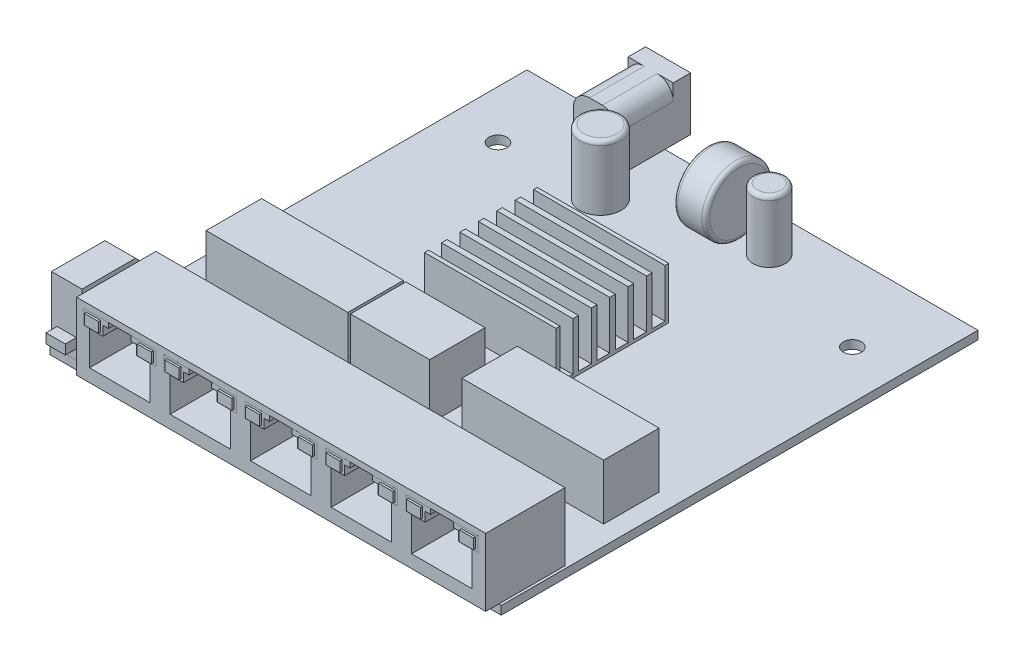
SolidWorks part; units mm, degrees
ref_plane "Front Plane" through (0, 0, 0) normal (0, 0, 1) x (1, 0, 0)
ref_plane "Top Plane" through (0, 0, 0) normal (0, 1, 0) x (1, 0, 0)
ref_plane "Right Plane" through (0, 0, 0) normal (1, 0, 0) x (0, 0, -1)
sketch "Sketch1" plane through (0, 0, 0) normal (0, 1, 0) x (1, 0, 0)
  line L1 (0, 0) -> (88.9, 0)
  line L2 (0, 0) -> (0, -93.98)
  line L3 (0, -93.98) -> (88.9, -93.98)
  line L4 (88.9, 0) -> (88.9, -93.98)
  dimension "D1" = 88.9
  dimension "D2" = 93.98
extrude "Extrude1" add sketch "Sketch1" along normal blind 1.651
sketch "Sketch2" plane through (0, 1.651, 0) normal (0, 1, 0) x (1, 0, 0)
  line L0 (0, -93.98) -> (88.9, -93.98) construction
  line L1 (0.254, -93.98) -> (6.2738, -93.98)
  line L2 (0.254, -93.98) -> (0.254, -80.264)
  line L3 (0.254, -80.264) -> (6.2738, -80.264)
  line L4 (6.2738, -93.98) -> (6.2738, -80.264)
  line L5 (0, 0) -> (0, -93.98) construction
  dimension "D1" = 6.0198
  dimension "D2" = 13.716
  dimension "D3" = 0.254
extrude "Extrude2" add sketch "Sketch2" along normal blind 12.7 separate body
chamfer "Chamfer1" distance 3.175 angle 45 1 edges at (3.2639, 14.351, 80.264)
sketch "Sketch3" plane through (0, 0, 93.98) normal (0, 0, 1) x (1, 0, 0)
  line L0 (0.254, 1.651) -> (6.2738, 1.651) construction
  line L1 (1.3589, 5.5245) -> (5.1689, 5.5245)
  line L2 (1.3589, 5.5245) -> (1.3589, 3.6195)
  line L3 (1.3589, 3.6195) -> (5.1689, 3.6195)
  line L4 (5.1689, 5.5245) -> (5.1689, 3.6195)
  line L5 (3.2639, 1.651) -> (3.2639, 3.6195) construction
  dimension "D1" = 3.81
  dimension "D2" = 1.905
  dimension "D3" = 1.9685
extrude "Extrude3" add sketch "Sketch3" along normal blind 2.1844
sketch "Sketch4" plane through (0, 1.651, 0) normal (0, 1, 0) x (1, 0, 0)
  line L1 (7.747, -80.899) -> (88.392, -80.899)
  line L2 (7.747, -80.899) -> (7.747, -96.52)
  line L3 (7.747, -96.52) -> (88.392, -96.52)
  line L4 (88.392, -80.899) -> (88.392, -96.52)
  line L5 (0, -93.98) -> (88.9, -93.98) construction
  line L7 (0, 0) -> (0, -93.98) construction
  dimension "D1" = 80.645
  dimension "D2" = 7.747
  dimension "D3" = 15.621
  dimension "D4" = 2.54
extrude "Extrude4" add sketch "Sketch4" along normal blind 13.335 separate body
sketch "Sketch6" plane through (0, 0, 96.52) normal (0, 0, 1) x (1, 0, 0)
  line L0 (7.747, 1.651) -> (88.392, 1.651) construction
  line L1 (7.747, 14.986) -> (7.747, 1.651) construction
  line L2 (16.256, 4.191) -> (16.256, 13.7922) construction
  line L4 (14.0208, 12.7762) -> (14.0208, 13.7922)
  line L5 (14.0208, 13.7922) -> (18.4912, 13.7922)
  line L6 (18.4912, 12.7762) -> (18.4912, 13.7922)
  line L7 (14.0208, 12.7762) -> (12.954, 12.7762)
  line L28 (10.287, 10.922) -> (10.287, 4.191)
  line L29 (10.287, 4.191) -> (22.225, 4.191)
  line L30 (22.225, 4.191) -> (22.225, 10.922)
  line L33 (19.558, 12.7762) -> (18.4912, 12.7762)
  line L60 (10.287, 10.922) -> (12.954, 10.922)
  line L61 (12.954, 10.922) -> (12.954, 12.7762)
  line L70 (19.558, 12.7762) -> (19.558, 10.922)
  line L71 (19.558, 10.922) -> (22.225, 10.922)
  dimension "D1" = 2.54
  dimension "D2" = 8.5852
  dimension "D3" = 6.731
  dimension "D4" = 11.938
  dimension "D5" = 6.604
  dimension "D6" = 2.54
  dimension "D7" = 4.4704
  dimension "D8" = 1.016
extrude "Cut-Extrude1" cut sketch "Sketch6" against normal blind 11.43
sketch "Sketch8" plane through (0, 0, 96.52) normal (0, 0, 1) x (1, 0, 0)
  line L0 (14.0208, 13.7922) -> (18.4912, 13.7922) construction
  line L1 (12.954, 10.922) -> (9.144, 10.922)
  line L2 (12.954, 10.922) -> (12.954, 12.7762)
  line L3 (12.954, 13.7922) -> (9.144, 13.7922)
  line L4 (9.144, 10.922) -> (9.144, 13.7922)
  line L5 (19.558, 10.922) -> (23.368, 10.922)
  line L6 (19.558, 10.922) -> (19.558, 12.7762)
  line L7 (19.558, 13.7922) -> (23.368, 13.7922)
  line L8 (23.368, 10.922) -> (23.368, 13.7922)
  line L9 (11.049, 13.7922) -> (11.049, 13.3731) construction
  line L10 (9.652, 13.3731) -> (12.446, 13.3731)
  line L11 (9.652, 13.3731) -> (9.652, 11.3411)
  line L12 (9.652, 11.3411) -> (12.446, 11.3411)
  line L13 (12.446, 13.3731) -> (12.446, 11.3411)
  line L14 (20.066, 13.3731) -> (22.86, 13.3731)
  line L15 (20.066, 13.3731) -> (20.066, 11.3411)
  line L16 (20.066, 11.3411) -> (22.86, 11.3411)
  line L17 (22.86, 13.3731) -> (22.86, 11.3411)
  line L18 (9.144, 12.3571) -> (9.652, 12.3571) construction
  line L19 (21.463, 13.7922) -> (21.463, 13.3731) construction
  line L21 (14.0208, 12.7762) -> (12.954, 12.7762)
  line L22 (14.0208, 12.7762) -> (14.0208, 13.7922)
  line L23 (14.0208, 13.7922) -> (12.954, 13.7922)
  line L25 (18.4912, 12.7762) -> (19.558, 12.7762)
  line L26 (18.4912, 12.7762) -> (18.4912, 13.7922)
  line L27 (18.4912, 13.7922) -> (19.558, 13.7922)
  dimension "D1" = 3.81
  dimension "D2" = 2.794
  dimension "D3" = 2.032
extrude "Extrude5" add sketch "Sketch8" along normal blind 0.3969 contours L13 L10 L11 L12 | L17 L14 L15 L16 region at (11.049, 12.3571, 96.52) region at (21.463, 12.3571, 96.52)
extrude "Extrude13" add sketch "Sketch8<3>" along normal blind 0.0013
sketch "Sketch8<3>" plane through (0, 0, 96.52) normal (0, 0, 1) x (1, 0, 0) same geometry as "Sketch8"
pattern_linear "LPattern2" count 5 spacing 15.875 along (1, 0, 0) of "Cut-Extrude1", "Extrude5", "Extrude13"
sketch "Sketch9" plane through (0, 1.651, 0) normal (0, 1, 0) x (1, 0, 0)
  line L0 (88.9, -93.98) -> (88.9, 0) construction
  line L1 (6.731, -59.055) -> (34.671, -59.055)
  line L2 (6.731, -59.055) -> (6.731, -69.977)
  line L3 (6.731, -69.977) -> (34.671, -69.977)
  line L4 (34.671, -59.055) -> (34.671, -69.977)
  line L5 (35.179, -59.055) -> (50.8, -59.055)
  line L6 (35.179, -59.055) -> (35.179, -69.977)
  line L7 (35.179, -69.977) -> (50.8, -69.977)
  line L8 (50.8, -59.055) -> (50.8, -69.977)
  line L9 (57.15, -59.055) -> (85.09, -59.055)
  line L10 (57.15, -59.055) -> (57.15, -69.977)
  line L11 (57.15, -69.977) -> (85.09, -69.977)
  line L12 (85.09, -59.055) -> (85.09, -69.977)
  line L13 (88.9, 0) -> (0, 0) construction
  dimension "D1" = 27.94
  dimension "D2" = 15.621
  dimension "D3" = 27.94
  dimension "D4" = 10.922
  dimension "D5" = 3.81
  dimension "D6" = 6.35
  dimension "D7" = 0.508
  dimension "D8" = 59.055
extrude "Extrude6" add sketch "Sketch9" along normal blind 10.922 separate body
sketch "Sketch10" plane through (0, 1.651, 0) normal (0, 1, 0) x (1, 0, 0)
  line L0 (88.9, -93.98) -> (88.9, 0) construction
  line L1 (31.242, -29.21) -> (57.15, -29.21)
  line L2 (31.242, -29.21) -> (31.242, -51.435)
  line L3 (31.242, -51.435) -> (57.15, -51.435)
  line L4 (57.15, -29.21) -> (57.15, -51.435)
  line L5 (88.9, 0) -> (0, 0) construction
  dimension "D1" = 25.908
  dimension "D2" = 22.225
  dimension "D3" = 31.75
  dimension "D4" = 29.21
extrude "Extrude7" add sketch "Sketch10" along normal blind 10.16 separate body
sketch "Sketch11" plane through (57.15, 0, 0) normal (1, 0, 0) x (0, 0, -1)
  line L0 (-51.435, 11.811) -> (-29.21, 11.811) construction
  line L1 (-50.6412, 11.811) -> (-48.1012, 11.811)
  line L2 (-50.6412, 11.811) -> (-50.6412, 2.286)
  line L3 (-50.6412, 2.286) -> (-48.1012, 2.286)
  line L4 (-48.1012, 11.811) -> (-48.1012, 2.286)
  line L5 (-51.435, 11.811) -> (-51.435, 1.651) construction
  dimension "D1" = 2.54
  dimension "D2" = 0.7937
  dimension "D3" = 9.525
extrude "Extrude8" cut sketch "Sketch11" against normal up to next (25.908 mm away)
pattern_linear "LPattern1" count 6 spacing 3.6322 along (0, 0, -1) of "Extrude8"
sketch "Sketch12" plane through (0, 1.651, 0) normal (0, 1, 0) x (1, 0, 0)
  line L0 (88.9, 0) -> (0, 0) construction
  line L1 (18.288, 5.08) -> (27.178, 5.08)
  line L2 (18.288, 5.08) -> (18.288, -9.144)
  line L3 (18.288, -9.144) -> (27.178, -9.144)
  line L4 (27.178, 5.08) -> (27.178, -9.144)
  line L5 (0, 0) -> (0, -93.98) construction
  dimension "D1" = 14.224
  dimension "D2" = 8.89
  dimension "D3" = 5.08
  dimension "D4" = 18.288
extrude "Extrude9" add sketch "Sketch12" along normal blind 10.541 separate body
sketch "Sketch14" plane through (0, 0, 9.144) normal (0, 0, 1) x (1, 0, 0)
  line L0 (18.288, 12.192) -> (27.178, 12.192) construction
  line L1 (21.463, 12.192) -> (18.288, 12.192)
  line L4 (18.288, 1.651) -> (27.178, 1.651)
  line L5 (27.178, 1.651) -> (27.178, 12.192)
  line L6 (27.178, 12.192) -> (18.288, 12.192)
  line L7 (18.288, 12.192) -> (18.288, 1.651)
  line L9 (27.178, 9.017) -> (27.178, 12.192)
  line L10 (27.178, 12.192) -> (24.003, 12.192)
  line L11 (18.288, 12.192) -> (18.288, 9.017)
  arc A0 (18.288, 9.017) -> (21.463, 12.192) centre (21.463, 9.017) cw
  arc A1 (24.003, 12.192) -> (27.178, 9.017) centre (24.003, 9.017) cw
  dimension "D2" = 3.175
  dimension "D1" = 0
extrude "Extrude10" cut sketch "Sketch14" against normal offset from surface (10.795 mm away) 3.429 up to face at (22.733, 6.9215, -5.08)
sketch "Sketch15" plane through (0, 0, -5.08) normal (0, 0, -1) x (-1, 0, 0)
  line L0 (-22.733, 1.651) -> (-22.733, 4.826) construction
  line L1 (-27.178, 1.651) -> (-18.288, 1.651) construction
  circle A0 centre (-22.733, 8.001) radius 3.175
  dimension "D2" = 6.35
  dimension "D1" = 3.175
extrude "Extrude11" cut sketch "Sketch15" against normal blind 8.89
sketch "Sketch16" plane through (0, 0, 3.81) normal (0, 0, -1) x (-1, 0, 0)
  circle A0 centre (-22.733, 8.001) radius 0.7937
  dimension "D1" = 1.5875
extrude "Extrude12" add sketch "Sketch16" along normal offset from surface (7.62 mm away) 1.27 up to face at (19.558, 8.001, -5.08)
fillet "Fillet1" radius 0.7937 1 edges at (23.5267, 8.001, -3.81)
hole_wizard "9/64 (0.14063) Diameter Hole1" positions "Sketch18" profile "Sketch17" hole size "9/64" standard "Ansi Inch" end condition through all
sketch "Sketch18" plane through (0, 1.651, 0) normal (0, 1, 0) x (-1, 0, 0)
  line L0 (-88.9, 0) -> (0, 0) construction
  line L1 (-44.45, 0) -> (-44.45, 16.0377) construction
  point P0 (-9.525, 15.24)
  point P2 (-79.375, 15.24)
  dimension "D1" = 69.85
  dimension "D2" = 15.24
sketch "Sketch17" plane through (9.525, 1.651, 15.24) normal (1, 0, 0) x (0, 0, 1)
  line L0 (0, 0) -> (0, 1.651)
  line L1 (0, 1.651) -> (1.786, 1.651)
  line L2 (1.786, 1.651) -> (1.786, 0)
  line L5 (1.786, 0) -> (0, 0)
  line L11 (0, -6.35) -> (0, 107.95) construction
  dimension "Thru Hole Dia." = 3.572
  dimension "Thru Hole Depth" = 1.651
sketch "Sketch19" plane through (0, 1.651, 0) normal (0, 1, 0) x (1, 0, 0)
  line L0 (0, 0) -> (0, -93.98) construction
  line L1 (88.9, 0) -> (0, 0) construction
  circle A0 centre (29.21, -14.732) radius 4.064
  dimension "D1" = 8.128
  dimension "D2" = 29.21
  dimension "D3" = 14.732
extrude "Extrude14" add sketch "Sketch19" along normal blind 12.7 separate body
fillet "Fillet2" radius 0.7937 1 edges at (29.21, 14.351, 18.796)
sketch "Sketch20" plane through (0, 1.651, 0) normal (0, 1, 0) x (1, 0, 0)
  line L0 (0, 0) -> (0, -93.98) construction
  line L1 (88.9, 0) -> (0, 0) construction
  circle A0 centre (55.372, -7.62) radius 3.175
  dimension "D1" = 6.35
  dimension "D2" = 55.372
  dimension "D3" = 7.62
extrude "Extrude15" add sketch "Sketch20" along normal blind 12.192 separate body
fillet "Fillet3" radius 0.7937 1 edges at (55.372, 13.843, 10.795)
ref_plane "Plane1" through (46.99, 0, 0) normal (-1, 0, 0) x (0, 0, 1)
sketch "Sketch21" plane through (46.99, 0, 0) normal (-1, 0, 0) x (0, 0, 1)
  line L0 (0, 1.651) -> (93.98, 1.651) construction
  line L2 (0, 1.651) -> (0, 0) construction
  circle A0 centre (8.255, 8.3185) radius 6.6675
  dimension "D1" = 13.335
  dimension "D2" = 8.255
extrude "Extrude16" add sketch "Sketch21" along normal mid plane 6.35 separate body
fillet "Fillet4" radius 0.7937 2 edges at (50.165, 8.3185, 14.9225) (43.815, 8.3185, 14.9225)
